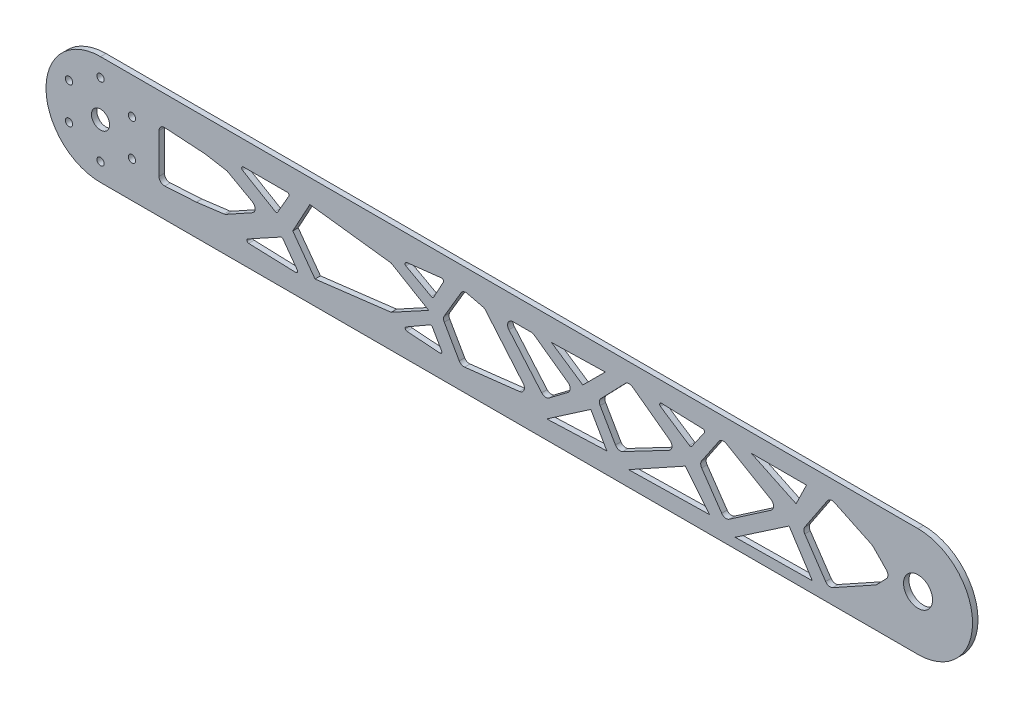
SolidWorks part; units mm, degrees
material "6061-T6 (SS)"
ref_plane "Front Plane" through (0, 0, 0) normal (0, 0, 1) x (1, 0, 0)
ref_plane "Top Plane" through (0, 0, 0) normal (0, 1, 0) x (1, 0, 0)
ref_plane "Right Plane" through (0, 0, 0) normal (1, 0, 0) x (0, 0, -1)
sketch "Sketch1" plane through (0, 0, 0) normal (0, 0, 1) x (1, 0, 0)
  line L0 (0, 0) -> (450, 0) construction
  line L1 (0, 30) -> (450, 30)
  line L2 (0, -30) -> (450, -30)
  arc A0 (0, 30) -> (0, -30) centre (0, 0) ccw
  arc A1 (450, -30) -> (450, 30) centre (450, 0) ccw
  circle A2 centre (0, 0) radius 20 construction
  circle A3 centre (0, 20) radius 2
  circle A4 centre (17.3205, 10) radius 2
  circle A5 centre (17.3205, -10) radius 2
  circle A6 centre (0, -20) radius 2
  circle A9 centre (0, 0) radius 5
  circle A10 centre (-17.3205, -10) radius 2
  circle A11 centre (-17.3205, 10) radius 2
  point P3 (225, 0)
  point P24 (0, 0)
  dimension "D1" = 30
  dimension "D3" = 40
  dimension "D4" = 4
  dimension "D6" = 10
  dimension "D2" = 450
  dimension "D5" = 6
extrude "Boss-Extrude1" add sketch "Sketch1" along normal blind 3
sketch "Sketch2" plane through (0, 0, 0) normal (0, 0, -1) x (-1, 0, 0)
  circle A0 centre (-450, 0) radius 8
  dimension "D1" = 16
extrude "Cut-Extrude1" cut sketch "Sketch2" against normal blind 10
sketch "Sketch3" plane through (0, 0, 0) normal (0, 0, -1) x (-1, 0, 0)
  line L0 (-225, 30) -> (-225, -30) construction
  line L1 (-450, 30) -> (0, 30) construction
  line L2 (0, -30) -> (-450, -30) construction
sketch "Sketch4" plane through (0, 0, 3) normal (0, 0, 1) x (1, 0, 0)
  line L3 (75.0512, 16.7519) -> (104.4964, 16.7519)
  line L4 (104.4964, 16.7519) -> (97.0103, 3.776)
  line L5 (97.0103, 3.776) -> (75.0512, 16.7519)
  line L6 (115.2364, 17.1336) -> (159.9949, 11.5901)
  line L7 (159.9949, 11.5901) -> (180.6552, -0.6182)
  line L8 (159.9949, -11.858) -> (118.0851, -16.9668)
  line L9 (118.0851, -16.9668) -> (105.8233, -0.1776)
  line L10 (105.8233, -0.1776) -> (115.2364, 17.1336)
  line L11 (189.6655, 18.5783) -> (182.9411, 6.2118)
  line L12 (189.6655, 18.5783) -> (165.3685, 15.767)
  line L13 (165.3685, 15.767) -> (182.9411, 6.2118)
  line L14 (199.5998, 18.5783) -> (188.3613, -0.4406)
  line L15 (188.3613, -0.4406) -> (198.4445, -18.0218)
  line L16 (198.4445, -18.0218) -> (236.2169, -13.6513)
  line L17 (236.2169, -13.6513) -> (211.3582, 15.767)
  line L18 (211.3582, 15.767) -> (199.5998, 18.5783)
  line L19 (220.5269, 17.1727) -> (237.9604, 17.1727)
  line L20 (237.9604, 17.1727) -> (260.5594, 1.0579)
  line L21 (244.6755, -10.9439) -> (220.5269, 17.1727)
  line L22 (265.4666, 6.2118) -> (277.8331, 18.5783)
  line L23 (277.8331, 18.5783) -> (248.2204, 17.8749)
  line L24 (248.2204, 17.8749) -> (265.4666, 6.2118)
  line L25 (165.3685, -16.3587) -> (182.2005, -6.7053)
  line L26 (182.2005, -6.7053) -> (188.6908, -18.0218)
  line L27 (188.6908, -18.0218) -> (165.3685, -16.3587)
  line L28 (245.6374, -19.8683) -> (269.8878, -3.2204)
  line L29 (269.8878, -3.2204) -> (278.7166, -18.6146)
  line L30 (278.7166, -18.6146) -> (245.6374, -19.8683)
  line L32 (290.6832, -21.5398) -> (321.9406, -4.2114)
  line L33 (321.9406, -4.2114) -> (335.2064, -20.704)
  line L34 (335.2064, -20.704) -> (290.6832, -21.5398)
  line L35 (341.9929, 19.1834) -> (329.7352, 1.0579)
  line L36 (329.7352, 1.0579) -> (343.6146, -19.1598)
  line L37 (343.6146, -19.1598) -> (373.065, 1.0579)
  line L38 (373.065, 1.0579) -> (341.9929, 19.1834)
  line L39 (244.6755, -10.9439) -> (260.5594, 1.0579)
  line L40 (273.8778, 3.1142) -> (290.6832, 20.5427)
  line L41 (290.6832, 20.5427) -> (317.2099, 1.0579)
  line L42 (317.2099, 1.0579) -> (284.8817, -15.8863)
  line L43 (284.8817, -15.8863) -> (273.8778, 3.1142)
  line L44 (305.3074, 19.271) -> (333.3759, 18.3243)
  line L45 (333.3759, 18.3243) -> (324.9421, 6.2118)
  line L46 (324.9421, 6.2118) -> (305.3074, 19.271)
  line L47 (358.198, 20.0502) -> (388.5975, 20.0502)
  line L48 (388.5975, 20.0502) -> (382.8865, 8.2928)
  line L49 (382.8865, 8.2928) -> (358.198, 20.0502)
  line L50 (349.331, -24.4281) -> (379.0302, -4.2114)
  line L51 (379.0302, -4.2114) -> (391.83, -23.927)
  line L52 (391.83, -23.927) -> (349.331, -24.4281)
  line L53 (386.543, -2.0485) -> (401.5864, 20.5696)
  line L54 (401.5864, 20.5696) -> (424.8813, 9.4759)
  line L55 (434.601, -0.4406) -> (424.8813, 9.4759)
  line L56 (434.601, -0.4406) -> (426.9833, -8.3408)
  line L57 (426.9833, -8.3408) -> (400.6645, -22.9126)
  line L58 (400.6645, -22.9126) -> (386.543, -2.0485)
  line L59 (159.9949, -11.858) -> (180.6552, -0.6182)
  line L60 (77.9082, -18.1131) -> (99.9591, -5.986)
  line L61 (99.9591, -5.986) -> (109.5177, -19.2166)
  line L62 (109.5177, -19.2166) -> (77.9082, -18.1131)
  line L63 (32.1814, 14.0452) -> (32.1814, -14.1865)
  line L64 (32.1814, -14.1865) -> (52.8225, -12.9556)
  line L65 (52.8225, -12.9556) -> (68.5544, -10.9439)
  line L66 (68.5544, -10.9439) -> (88.303, 0)
  line L67 (88.303, 0) -> (69.6625, 10.3469)
  line L68 (69.6625, 10.3469) -> (57.5717, 12.4236)
  line L69 (57.5717, 12.4236) -> (32.1814, 14.0452)
extrude "Cut-Extrude2" cut sketch "Sketch4" against normal blind 10
fillet "Fillet1" radius 3 7 edges at (57.5717, 12.4236, 1.5) (69.6625, 10.3469, 1.5) (88.303, 0, 1.5) (52.8225, -12.9556, 1.5) (68.5544, -10.9439, 1.5) (32.1814, -14.1865, 1.5) (32.1814, 14.0452, 1.5)
fillet "Fillet2" radius 1 15 edges at (324.9421, 6.2118, 1.5) (333.3759, 18.3243, 1.5) (305.3074, 19.271, 1.5) (189.6655, 18.5783, 1.5) (182.9411, 6.2118, 1.5) (165.3685, 15.767, 1.5) (182.2005, -6.7053, 1.5) (188.6908, -18.0218, 1.5) (165.3685, -16.3587, 1.5) (109.5177, -19.2166, 1.5) (99.9591, -5.986, 1.5) (77.9082, -18.1131, 1.5) (97.0103, 3.776, 1.5) (104.4964, 16.7519, 1.5) (75.0512, 16.7519, 1.5)
fillet "Fillet3" radius 3 23 edges at (400.6645, -22.9126, 1.5) (401.5864, 20.5696, 1.5) (260.5594, 1.0579, 1.5) (220.5269, 17.1727, 1.5) (244.6755, -10.9439, 1.5) (343.6146, -19.1598, 1.5) (284.8817, -15.8863, 1.5) (317.2099, 1.0579, 1.5) (236.2169, -13.6513, 1.5) (237.9604, 17.1727, 1.5) (211.3582, 15.767, 1.5) (199.5998, 18.5783, 1.5) (341.9929, 19.1834, 1.5) (290.6832, 20.5427, 1.5) (198.4445, -18.0218, 1.5) (188.3613, -0.4406, 1.5) (273.8778, 3.1142, 1.5) (329.7352, 1.0579, 1.5) (386.543, -2.0485, 1.5) (424.8813, 9.4759, 1.5) (426.9833, -8.3408, 1.5) (434.601, -0.4406, 1.5) (373.065, 1.0579, 1.5)
